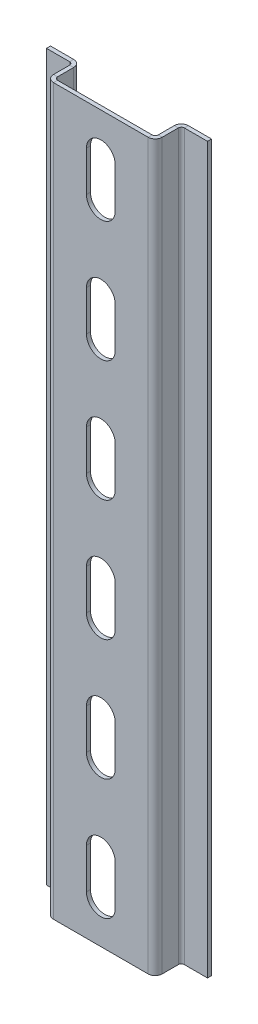
SolidWorks part; units mm, degrees
note: The reader was unsure of these and kept them because the rebuilt part matched: flange length of "边线-法兰1", "边线-法兰2".
ref_plane "前视基准面" through (0, 0, 0) normal (0, 0, 1) x (1, 0, 0)
ref_plane "上视基准面" through (0, 0, 0) normal (0, 1, 0) x (1, 0, 0)
ref_plane "右视基准面" through (0, 0, 0) normal (1, 0, 0) x (0, 0, -1)
sketch "草图2" plane through (0, 0, 0) normal (0, 0, 1) x (1, 0, 0)
  line L1 (-12.4454, -19.2153) -> (14.5546, -19.2153)
  line L2 (-12.4454, -19.2153) -> (-12.4454, -199.2153)
  line L3 (-12.4454, -199.2153) -> (14.5546, -199.2153)
  line L4 (14.5546, -19.2153) -> (14.5546, -199.2153)
  dimension "D1" = 27
  dimension "D2" = 180
sheet metal parameters "钣金1" thickness 1 parameters "D1"=0.7366
base flange "基体-法兰1" sketch "草图2" thickness 1 reverse thickness direction no parameters "D1"=0.7366
edge flange "边线-法兰1" sketch "草图9" flange profiles "草图9", "草图10" flange angle 90 flange length 7.5 flange position material inside bend radius 0.7366 thickness 1 relief rectangular parameters "D6"=10, "D8"=1
sketch "草图9" plane through (-12.4454, 0, -1) normal (-1, 0, 0) x (0, 1, 0)
  line L2 (-199.2153, 0) -> (-199.2153, 6.5)
  line L3 (-199.2153, 6.5) -> (-19.2153, 6.5)
  line L4 (-19.2153, 6.5) -> (-19.2153, 0)
  line L7 (-19.2153, 0) -> (-199.2153, 0) construction
  line L8 (-19.2153, 0) -> (-199.2153, 0)
sketch "草图10" plane through (14.5546, 0, -1) normal (1, 0, 0) x (0, -1, 0)
  line L0 (199.2153, 0) -> (19.2153, 0) construction
  line L1 (199.2153, 0) -> (19.2153, 0)
  line L2 (19.2153, 0) -> (19.2153, 6.5)
  line L3 (19.2153, 6.5) -> (199.2153, 6.5)
  line L4 (199.2153, 6.5) -> (199.2153, 0)
bend "边线折弯1" bend radius 0.7366 bend angle 90 parameters "D5"=1
bend "边线折弯2" bend radius 0.7366 bend angle 90 parameters "D5"=2
edge flange "边线-法兰2" sketch "草图15" flange profiles "草图15", "草图16" flange angle 90 flange length 7.5 flange position material inside bend radius 0.7366 thickness 1 relief rectangular parameters "D6"=10, "D8"=1
sketch "草图15" plane through (-12.4454, 0, -7.5) normal (0, 0, -1) x (0, -1, 0)
  line L0 (19.2153, 0) -> (199.2153, 0) construction
  line L1 (19.2153, 0) -> (199.2153, 0)
  line L2 (19.2153, 0) -> (19.2153, 6.5)
  line L3 (19.2153, 6.5) -> (199.2153, 6.5)
  line L4 (199.2153, 6.5) -> (199.2153, 0)
sketch "草图16" plane through (14.5546, 0, -7.5) normal (0, 0, -1) x (0, 1, 0)
  line L0 (-199.2153, 0) -> (-19.2153, 0) construction
  line L1 (-199.2153, 0) -> (-19.2153, 0)
  line L2 (-199.2153, 0) -> (-199.2153, 6.5)
  line L3 (-199.2153, 6.5) -> (-19.2153, 6.5)
  line L4 (-19.2153, 6.5) -> (-19.2153, 0)
bend "边线折弯3" bend radius 0.7366 bend angle 90 parameters "D5"=3
bend "边线折弯4" bend radius 0.7366 bend angle 90 parameters "D5"=4
sketch "草图17" plane through (0, 0, 0) normal (0, 0, 1) x (1, 0, 0)
  line L0 (1.0546, -199.2153) -> (1.0546, -19.2153) construction
  line L1 (-10.7088, -199.2153) -> (12.818, -199.2153) construction
  line L2 (12.818, -19.2153) -> (-10.7088, -19.2153) construction
  line L3 (4.6268, -189.2153) -> (4.6268, -179.2153)
  line L4 (-2.5177, -189.2153) -> (-2.5177, -179.2153)
  arc A0 (-2.5177, -189.2153) -> (4.6268, -189.2153) centre (1.0546, -189.2153) ccw
  arc A1 (4.6268, -179.2153) -> (-2.5177, -179.2153) centre (1.0546, -179.2153) ccw
  dimension "D1" = 10
  dimension "D2" = 10
extrude "切除-拉伸3" cut sketch "草图17" against normal blind 10 normal cut yes
pattern_linear "阵列(线性)1" count 9 spacing 30 along (0, 1, 0) of "切除-拉伸3"
flat pattern "平板型式1" [suppressed]
sketch "折弯-线1" plane through (0, 0, 0) normal (0, 0, 1) x (1, 0, 0)
  line L0 (13.7892, -199.2153) -> (13.7892, -19.2153) construction
  line L1 (-11.6801, -19.2153) -> (-11.6801, -199.2153) construction
  line L2 (13.7892, -199.2153) -> (13.7892, -19.2153) construction
  line L3 (-11.6801, -19.2153) -> (-11.6801, -199.2153) construction
  line L4 (19.7584, -199.2153) -> (19.7584, -19.2153) construction
  line L5 (-17.6493, -19.2153) -> (-17.6493, -199.2153) construction
  line L6 (19.7584, -199.2153) -> (19.7584, -19.2153) construction
  line L7 (-17.6493, -19.2153) -> (-17.6493, -199.2153) construction
sketch3d "边界框1" [suppressed]
  line L0 (26.4931, -19.2153, 0) -> (26.4931, -199.2153, 0) construction
  line L1 (-24.3839, -19.2153, 0) -> (-24.3839, -199.2153, 0) construction
  line L2 (26.4931, -19.2153, 0) -> (-24.3839, -19.2153, 0) construction
  line L3 (26.4931, -199.2153, 0) -> (-24.3839, -199.2153, 0) construction
bend of the flat pattern "展平-<边线折弯1>1"
bend of the flat pattern "展平-<边线折弯2>1"
bend of the flat pattern "展平-<边线折弯3>1"
bend of the flat pattern "展平-<边线折弯4>1"
